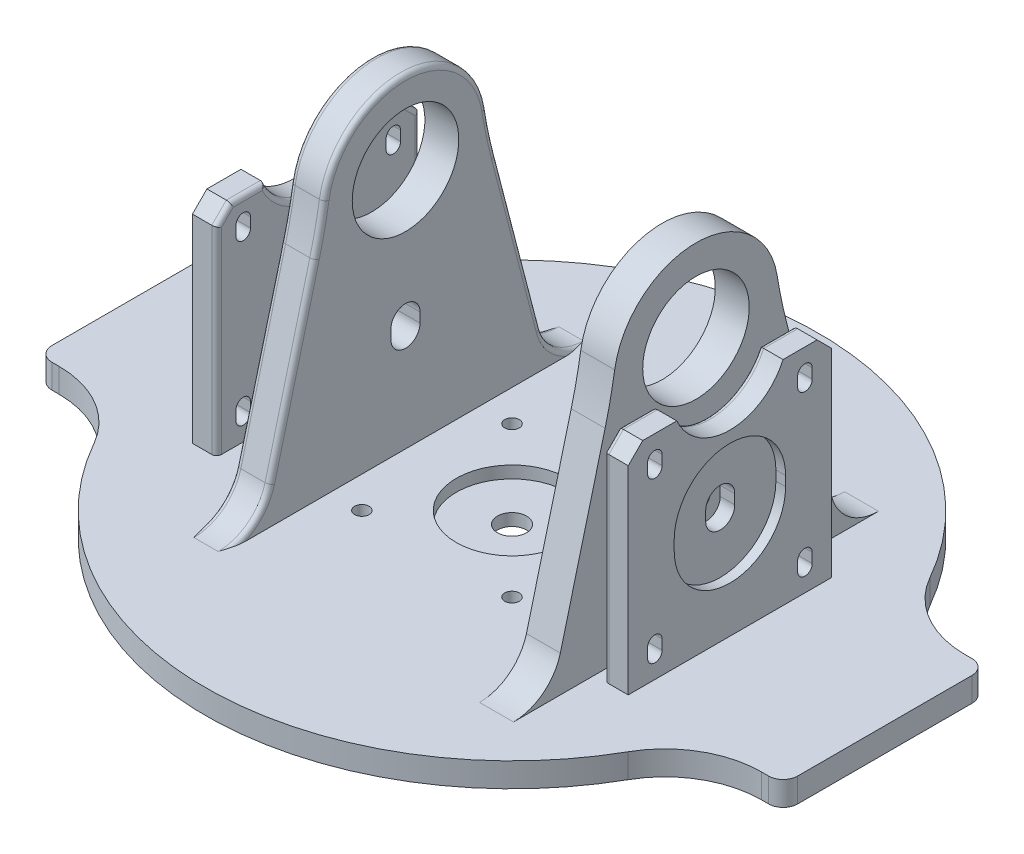
SolidWorks part; units mm, degrees
ref_plane "Front Plane" through (0, 0, 0) normal (0, 0, 1) x (1, 0, 0)
ref_plane "Top Plane" through (0, 0, 0) normal (0, 1, 0) x (1, 0, 0)
ref_plane "Right Plane" through (0, 0, 0) normal (1, 0, 0) x (0, 0, -1)
sketch "Sketch1" plane through (0, 0, 0) normal (0, 1, 0) x (1, 0, 0)
  line L1 (-21, -21) -> (21, -21) construction
  line L2 (-21, -21) -> (-21, 21) construction
  line L3 (-21, 21) -> (21, 21) construction
  line L4 (21, -21) -> (21, 21) construction
  line L5 (-21, -21) -> (21, 21) construction
  line L6 (-21, 21) -> (21, -21) construction
  line L7 (74, 21) -> (72.5674, 21)
  line L8 (77, 18) -> (77, -18)
  line L9 (74, -21) -> (72.5674, -21)
  line L11 (-72.5674, 21) -> (-74, 21)
  line L13 (-72.5674, -21) -> (-74, -21)
  line L14 (-77, 18) -> (-77, -18)
  circle A0 centre (0, 0) radius 3
  circle A1 centre (15.5, 15.5) radius 1.5
  circle A2 centre (15.5, -15.5) radius 1.5
  circle A3 centre (-15.5, -15.5) radius 1.5
  circle A4 centre (-15.5, 15.5) radius 1.5
  arc A5 (-55.1545, -31.1618) -> (55.1545, -31.1618) centre (0, 0) ccw
  arc A6 (55.1545, 31.1618) -> (-55.1545, 31.1618) centre (0, 0) ccw
  arc A7 (-72.5674, 21) -> (-55.1545, 31.1618) centre (-72.5674, 41) ccw
  arc A8 (-72.5674, -21) -> (-55.1545, -31.1618) centre (-72.5674, -41) cw
  arc A9 (55.1545, -31.1618) -> (72.5674, -21) centre (72.5674, -41) cw
  arc A10 (72.5674, 21) -> (55.1545, 31.1618) centre (72.5674, 41) cw
  arc A11 (77, 18) -> (74, 21) centre (74, 18) ccw
  arc A12 (77, -18) -> (74, -21) centre (74, -18) cw
  arc A13 (-77, -18) -> (-74, -21) centre (-74, -18) ccw
  arc A14 (-77, 18) -> (-74, 21) centre (-74, 18) cw
  point P18 (0, 0)
  point P36 (59.7669, 21)
  point P39 (77, 21)
  point P44 (-77, -21)
  dimension "D1" = 6
  dimension "D5" = 3
  dimension "D7" = 20
  dimension "D8" = 3
  dimension "D2" = 42
  dimension "D3" = 42
  dimension "D4" = 5.5
  dimension "D6" = 4
extrude "Boss-Extrude1" add sketch "Sketch1" along normal blind 5
sketch "Sketch2" plane through (0, 5, 0) normal (0, 1, 0) x (1, 0, 0)
  circle A0 centre (0, 0) radius 11.5
  dimension "D1" = 23
extrude "Cut-Extrude1" cut sketch "Sketch2" against normal blind 2.5
sketch "Sketch3" plane through (0, 5, 0) normal (0, 1, 0) x (1, 0, 0)
  line L0 (0, 0) -> (0, 17.4199) construction
  line L1 (-21, -21) -> (21, -21) construction
  line L2 (-21, -21) -> (-21, 21) construction
  line L3 (-21, 21) -> (21, 21) construction
  line L4 (21, -21) -> (21, 21) construction
  line L5 (-21, -21) -> (21, 21) construction
  line L6 (-21, 21) -> (21, -21) construction
  line L7 (21, -2.5) -> (40, -2.5) construction
  line L8 (21, -2.5) -> (21, 2.5) construction
  line L9 (21, 2.5) -> (40, 2.5) construction
  line L10 (40, -2.5) -> (40, 2.5) construction
  line L11 (-40, -2.5) -> (-40, 2.5) construction
  line L12 (-21, 2.5) -> (-40, 2.5) construction
  line L13 (-21, -2.5) -> (-40, -2.5) construction
  line L14 (40, 21) -> (40, -21)
  line L15 (40, -21) -> (45, -21)
  line L16 (45, -21) -> (45, 21)
  line L17 (45, 21) -> (40, 21)
  line L18 (-45, 21) -> (-40, 21)
  line L19 (-45, -21) -> (-45, 21)
  line L20 (-40, -21) -> (-45, -21)
  line L21 (-40, 21) -> (-40, -21)
  point P0 (0, 0)
  point P6 (21, 0)
  point P19 (45, 0)
  dimension "D1" = 42
  dimension "D2" = 42
  dimension "D3" = 19
  dimension "D4" = 5
  dimension "D5" = 5
  dimension "D6" = 42
extrude "Boss-Extrude2" add sketch "Sketch3" along normal blind 44
sketch "Sketch4" plane through (-45, 0, 0) normal (-1, 0, 0) x (0, 0, 1)
  line L0 (-21, 49) -> (21, 5) construction
  line L1 (21, 49) -> (21, 5) construction
  line L2 (21, 49) -> (-21, 5) construction
  line L3 (-21, 49) -> (21, 49) construction
  line L4 (18, 49) -> (21, 46)
  line L5 (21, 49) -> (21, 5) construction
  line L6 (21, 46) -> (21, 49)
  line L7 (21, 49) -> (18, 49)
  line L8 (0, 27) -> (0, 81.2059) construction
  line L9 (-21, 46) -> (-21, 49)
  line L10 (-21, 49) -> (-18, 49)
  line L11 (-18, 49) -> (-21, 46)
  line L12 (-21, 49) -> (-21, 5) construction
  line L13 (-17, 44.5) -> (-17, 42.5)
  line L14 (-14, 44.5) -> (-14, 42.5)
  line L15 (17, 44.5) -> (17, 42.5)
  line L16 (14, 44.5) -> (14, 42.5)
  line L17 (0, 27) -> (5.914, 27) construction
  line L18 (-17, 9.5) -> (-17, 11.5)
  line L19 (-14, 9.5) -> (-14, 11.5)
  line L20 (14, 9.5) -> (14, 11.5)
  line L21 (17, 9.5) -> (17, 11.5)
  line L22 (0, 28) -> (0, 26) construction
  line L23 (3, 28) -> (3, 26)
  line L24 (-3, 28) -> (-3, 26)
  line L25 (-21, 5) -> (21, 5) construction
  arc A0 (3, 28) -> (-3, 28) centre (0, 28) ccw
  arc A1 (17, 42.5) -> (14, 42.5) centre (15.5, 42.5) cw
  arc A2 (14, 44.5) -> (17, 44.5) centre (15.5, 44.5) cw
  arc A3 (-17, 11.5) -> (-14, 11.5) centre (-15.5, 11.5) cw
  arc A4 (-14, 9.5) -> (-17, 9.5) centre (-15.5, 9.5) cw
  arc A5 (-14, 44.5) -> (-17, 44.5) centre (-15.5, 44.5) ccw
  arc A6 (14, 9.5) -> (17, 9.5) centre (15.5, 9.5) ccw
  circle A7 centre (0, 53.86) radius 12
  arc A8 (-17, 42.5) -> (-14, 42.5) centre (-15.5, 42.5) ccw
  arc A9 (17, 11.5) -> (14, 11.5) centre (15.5, 11.5) ccw
  arc A11 (-3, 26) -> (3, 26) centre (0, 26) ccw
  point P24 (0, 26)
  dimension "D1" = 3
  dimension "D2" = 4.5
  dimension "D7" = 1.5
  dimension "D9" = 3
  dimension "D10" = 2
  dimension "D11" = 2
  dimension "D15" = 24
  dimension "D3" = 2
  dimension "D5" = 3
  dimension "D6" = 3
  dimension "D4" = 5.5
  dimension "D8" = 2
  dimension "D14" = 48.86
extrude "Cut-Extrude3" cut sketch "Sketch4" against normal through all
sketch "Sketch6" plane through (45, 0, 0) normal (1, 0, 0) x (0, 0, -1)
  line L0 (11.5, 28) -> (11.5, 26)
  line L1 (-11.5, 28) -> (-11.5, 26)
  arc A0 (11.5, 28) -> (-11.5, 28) centre (0, 28) ccw
  arc A1 (-11.5, 26) -> (11.5, 26) centre (0, 26) ccw
  dimension "D1" = 23
  dimension "D2" = 23
  dimension "D3" = 2
  dimension "D4" = 2
sketch "Sketch7" plane through (-45, 0, 0) normal (-1, 0, 0) x (0, 0, 1)
  line L2 (-11.5, 28) -> (-11.5, 26)
  line L3 (11.5, 26) -> (11.5, 28)
  line L4 (-11.5, 28) -> (-11.5, 26)
  line L5 (11.5, 26) -> (11.5, 28)
  arc A2 (-11.5, 26) -> (11.5, 26) centre (0, 26) ccw
  arc A3 (11.5, 28) -> (-11.5, 28) centre (0, 28) ccw
  arc A4 (-11.5, 26) -> (11.5, 26) centre (0, 26) ccw
  arc A5 (11.5, 28) -> (-11.5, 28) centre (0, 28) ccw
  dimension "D1" = 0
extrude "Cut-Extrude4" cut sketch "Sketch7" against normal blind 2
extrude "Cut-Extrude5" cut sketch "Sketch6" against normal blind 2
sketch "Sketch8" plane through (0, 5, 0) normal (0, 1, 0) x (1, 0, 0)
  line L1 (-21.9927, 29.9572) -> (-28.9927, 29.9572)
  line L2 (-21.9927, 29.9572) -> (-21.9927, -29.9572)
  line L3 (-21.9927, -29.9572) -> (-28.9927, -29.9572)
  line L4 (-28.9927, 29.9572) -> (-28.9927, -29.9572)
  point P4 (-21.9927, 0)
  point P5 (0, 0)
  dimension "D1" = 7
extrude "Boss-Extrude3" add sketch "Sketch8" along normal blind 70
sketch "Sketch9" plane through (-28.9927, 0, 0) normal (-1, 0, 0) x (0, 0, 1)
  line L0 (-18.7655, 48.0662) -> (-29.9572, 5)
  line L2 (-29.9572, 75) -> (-29.9572, 5) construction
  line L3 (18.7655, 48.0662) -> (29.9572, 5)
  line L5 (3, 28) -> (3, 26) construction
  line L6 (-3, 26) -> (-3, 28) construction
  line L7 (3, 28) -> (3, 26)
  line L8 (-3, 26) -> (-3, 28)
  line L9 (-29.9572, 5) -> (29.9572, 5) construction
  circle A0 centre (0, 54.86) radius 11
  arc A1 (16.7894, 57.5274) -> (-16.7894, 57.5274) centre (0, 54.86) ccw
  arc A2 (18.7655, 48.0662) -> (16.7894, 57.5274) centre (115.5508, 73.2179) cw
  arc A3 (-18.7655, 48.0662) -> (-16.7894, 57.5274) centre (-115.5508, 73.2179) ccw
  arc A4 (-3, 26) -> (3, 26) centre (0, 26) ccw construction
  arc A5 (3, 28) -> (-3, 28) centre (0, 28) ccw construction
  arc A6 (-3, 26) -> (3, 26) centre (0, 26) ccw
  arc A7 (3, 28) -> (-3, 28) centre (0, 28) ccw
  point P14 (17, 54.86)
  point P17 (-17, 54.86)
  line M3 (29.9572, 5) -> (29.9572, 75)
  line M4 (29.9572, 75) -> (-29.9572, 75)
  line M5 (-29.9572, 75) -> (-29.9572, 5)
  dimension "D1" = 22
  dimension "D2" = 34
  dimension "D3" = 100
  dimension "D4" = 49.86
extrude "Cut-Extrude6" cut sketch "Sketch9" against normal blind 8 contours L0 A3 A1 A2 L3 M3 M4 M5 | A0 | L7 A7 L8 A6 region at (-28.9927, 26.7648, -25.2531) region at (-28.9927, 27, 0) region at (-28.9927, 54.86, 0)
fillet "Fillet1" radius 10 2 edges at (-25.4927, 5, 29.9572) (-25.4927, 5, -29.9572)
fillet "Fillet2" radius 1 28 edges at (-28.9927, 7.0895, 31.5731) (-28.9927, 30.2755, 23.3888) (-28.9927, 52.7729, 17.6631) (-28.9927, 7.0895, -31.5731) (-28.9927, 30.2755, -23.3888) (-28.9927, 52.7729, -17.6631) (-21.9927, 7.0895, 31.5731) (-21.9927, 30.2755, 23.3888) (-21.9927, 52.7729, 17.6631) (-21.9927, 7.0895, -31.5731) (-21.9927, 30.2755, -23.3888) (-21.9927, 52.7729, -17.6631) (40, 25.5, 21) (40, 47.5, 19.5) (40, 49, 14.4859) (40, 41.86, 0) (40, 49, -14.4859) (40, 47.5, -19.5) (40, 25.5, -21) (-40, 49, 14.4859) (-40, 47.5, 19.5) (-40, 25.5, 21) (-40, 25.5, -21) (-40, 47.5, -19.5) (-40, 49, -14.4859) (-40, 41.86, 0) (-28.9927, 71.86, 0) (-21.9927, 71.86, 0)
ref_plane "Plane1" through (4.5, 0, 0) normal (1, 0, 0) x (0, 0, -1)
mirror "Mirror1" about plane through (4.5, 0, 0) normal (1, 0, 0) of "Cut-Extrude6", "Boss-Extrude3", "Fillet1"
